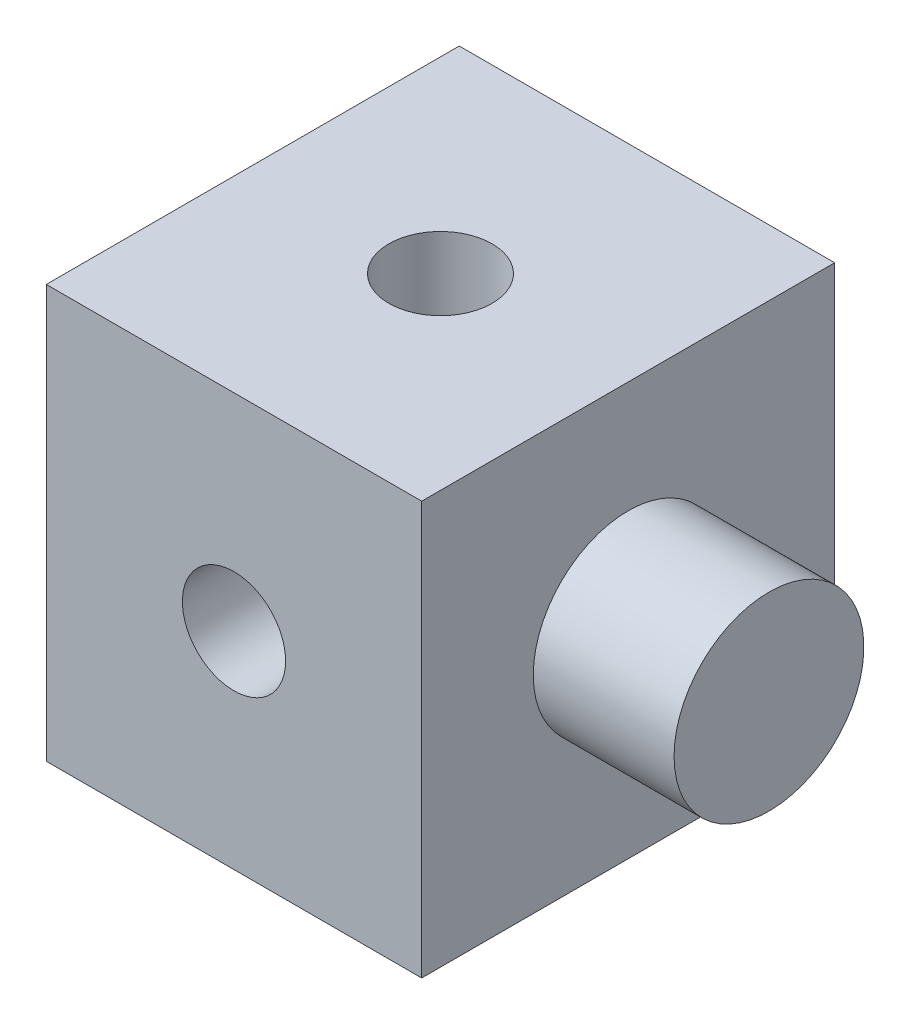
SolidWorks part; units mm, degrees
ref_plane "Front Plane" through (0, 0, 0) normal (0, 0, 1) x (1, 0, 0)
ref_plane "Top Plane" through (0, 0, 0) normal (0, 1, 0) x (1, 0, 0)
ref_plane "Right Plane" through (0, 0, 0) normal (1, 0, 0) x (0, 0, -1)
sketch "Block Sketch" plane through (0, 0, 0) normal (0, 0, 1) x (1, 0, 0)
  line L0 (-40, -22) -> (0, -22)
  line L1 (0, -22) -> (0, 22)
  line L2 (0, 22) -> (-40, 22)
  line L3 (-40, 22) -> (-40, -22)
extrude "Block" add sketch "Block Sketch" along normal mid plane 44
ref_axis "Engine Axis" through (17.75, 0, 0) along (-1, 0, 0)
sketch "Neck Sketch" plane through (0, 0, 0) normal (0, 0, 1) x (1, 0, 0)
  line L0 (-1000, 0) -> (1000, 0) construction
  line L1 (0, 0) -> (15, 0)
  line L2 (15, 0) -> (15, 10.1125)
  line L3 (15, 10.1125) -> (0, 10.1125)
  line L4 (0, 10.1125) -> (0, 0)
revolve "Neck" add sketch "Neck Sketch" angle 360 about L0
sketch "Regulator Port Sketch" plane through (0, 0, 0) normal (0, 0, 1) x (1, 0, 0)
  line L0 (-1000, 0) -> (1000, 0) construction
  line L1 (-41, 0) -> (-26, 0)
  line L2 (-26, 0) -> (-26, 7.2)
  line L3 (-26, 7.2) -> (-41, 7.2)
  line L4 (-41, 7.2) -> (-41, 0)
revolve "Regulator Port" cut sketch "Regulator Port Sketch" angle 360 about L0
sketch "Side Port +Y Sketch" plane through (0, 0, 0) normal (0, 0, 1) x (1, 0, 0)
  line L0 (-20, -40) -> (-20, 40) construction
  line L1 (-20, 8) -> (-14.5, 8)
  line L2 (-14.5, 8) -> (-14.5, 23)
  line L3 (-14.5, 23) -> (-20, 23)
  line L4 (-20, 23) -> (-20, 8)
revolve "Side Port +Y" cut sketch "Side Port +Y Sketch" angle 360 about L0
sketch "Side Port -Y Sketch" plane through (0, 0, 0) normal (0, 0, 1) x (1, 0, 0)
  line L0 (-20, -40) -> (-20, 40) construction
  line L1 (-20, -23) -> (-14.5, -23)
  line L2 (-14.5, -23) -> (-14.5, -8)
  line L3 (-14.5, -8) -> (-20, -8)
  line L4 (-20, -8) -> (-20, -23)
revolve "Side Port -Y" cut sketch "Side Port -Y Sketch" angle 360 about L0
sketch "Side Port +Z Sketch" plane through (0, 0, 0) normal (0, 0, 1) x (1, 0, 0)
  circle A0 centre (-20, 0) radius 5.5
extrude "Side Port +Z" cut sketch "Side Port +Z Sketch" along normal blind 23
sketch "Side Port -Z Sketch" plane through (0, 0, 0) normal (0, 0, 1) x (1, 0, 0)
  circle A0 centre (-20, 0) radius 5.5
extrude "Side Port -Z" cut sketch "Side Port -Z Sketch" against normal blind 23
